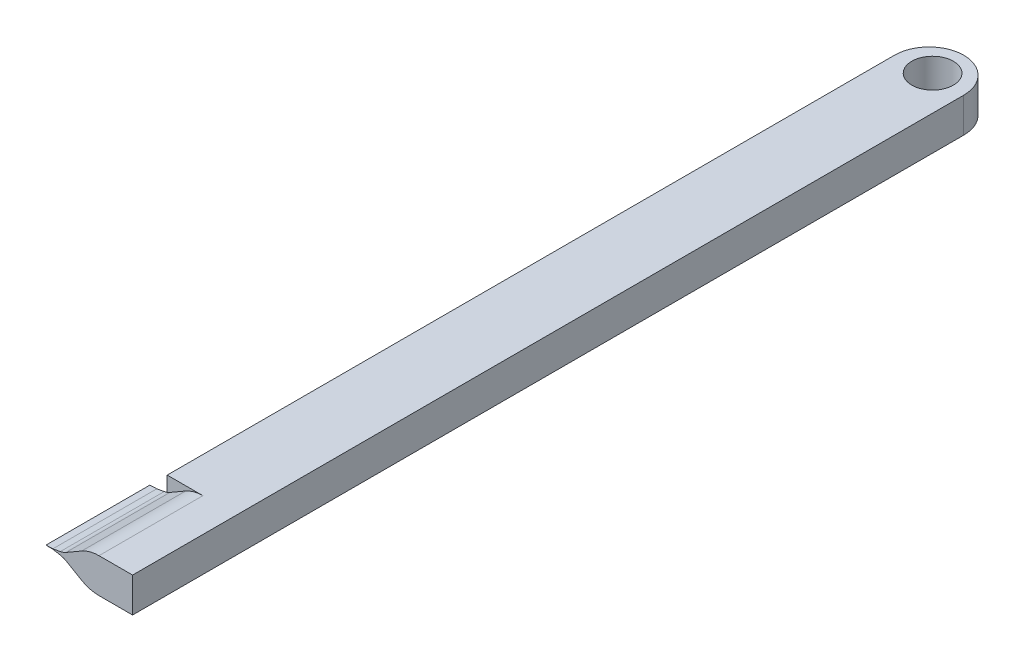
SolidWorks part; units mm, degrees
ref_plane "Front Plane" through (0, 0, 0) normal (0, 0, 1) x (1, 0, 0)
ref_plane "Top Plane" through (0, 0, 0) normal (0, 1, 0) x (1, 0, 0)
ref_plane "Right Plane" through (0, 0, 0) normal (1, 0, 0) x (0, 0, -1)
sketch "Sketch2" plane through (0, 0, 0) normal (0, 0, 1) x (1, 0, 0)
  line L1 (0, 0) -> (20, 0)
  line L2 (0, 0) -> (0, 10)
  line L3 (0, 10) -> (20, 10)
  line L4 (20, 0) -> (20, 10)
  dimension "D1" = 10
  dimension "D2" = 20
extrude "Boss-Extrude1" add sketch "Sketch2" along normal blind 250
sketch "Sketch3" plane through (0, 10, 0) normal (0, 1, 0) x (1, 0, 0)
  line L0 (20, 0) -> (0, 0) construction
  circle A0 centre (10, -9) radius 6
  point P2 (10, 0)
  dimension "D1" = 12
  dimension "D2" = 9
extrude "Cut-Extrude1" cut sketch "Sketch3" against normal blind 30
fillet "Fillet1" radius 10 1 edges at (20, 5, 0)
fillet "Fillet3" radius 10 1 edges at (0, 5, 0)
sketch "Sketch4" plane through (0, 0, 0) normal (-1, 0, 0) x (0, 0, 1)
  line L0 (250, 0) -> (10, 0) construction
  line L1 (220, 0) -> (250, 0)
  line L2 (220, 0) -> (220, 10)
  line L3 (220, 10) -> (250, 10)
  line L4 (250, 0) -> (250, 10)
  dimension "D1" = 30
extrude "Boss-Extrude2" add sketch "Sketch4" along normal blind 5
sketch "Sketch5" plane through (0, 0, 250) normal (0, 0, 1) x (1, 0, 0)
  line L0 (-5, 5) -> (-3, 5.0698)
  line L1 (-5, 0) -> (-5, 10) construction
  line L2 (-3, 5.0698) -> (0, 5.5988)
  line L3 (0, 5.5988) -> (7.6231, 10)
  line L4 (20, 10) -> (-5, 10) construction
  line L5 (7.6231, 10) -> (7.6231, 0)
  line L6 (-5, 5) -> (6.83, 5) construction
  line L7 (0, 4.4012) -> (7.6231, 0)
  line L8 (-5, 5) -> (-3, 4.9302)
  line L9 (-3, 4.9302) -> (0, 4.4012)
  line L10 (-5, 5) -> (-5, 10)
  line L11 (-5, 10) -> (7.6231, 10)
  line L12 (-5, 5) -> (-5, 0)
  line L13 (-5, 0) -> (7.6231, 0)
  point P11 (7.6231, 5)
  line M6 (20, 10) -> (-5, 10)
  line M7 (-5, 10) -> (-5, 0)
  line M8 (-5, 0) -> (20, 0)
  dimension "D1" = 3
  dimension "D2" = 2
  dimension "D3" = 2
  dimension "D4" = 10
  dimension "D5" = 30
extrude "Cut-Extrude2" cut sketch "Sketch5" against normal blind 30 contours L2 L3 L0 M6 M7 | L9 L8 L7 M7 M8 region at (-0.4548, 7.9866, 250) region at (-0.4548, 2.0134, 250)
fillet "Fillet4" radius 5 2 edges at (0, 5.5988, 235) (0, 4.4012, 235)
fillet "Fillet5" radius 10 2 edges at (7.6231, 0, 235) (7.6231, 10, 235)
